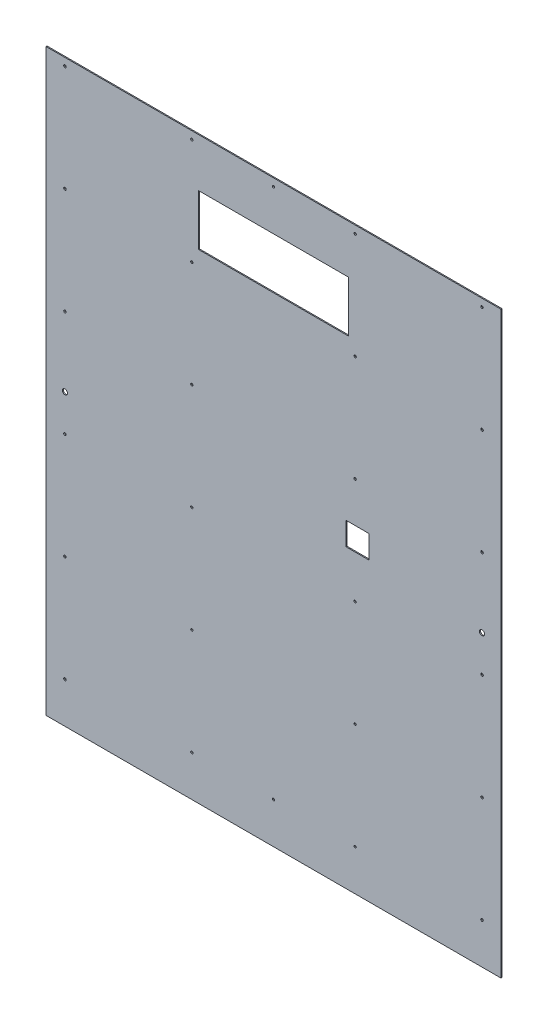
SolidWorks part; units mm, degrees
ref_plane "Спереди" through (0, 0, 0) normal (0, 0, 1) x (1, 0, 0)
ref_plane "Сверху" through (0, 0, 0) normal (0, 1, 0) x (1, 0, 0)
ref_plane "Справа" through (0, 0, 0) normal (1, 0, 0) x (0, 0, -1)
sketch "Эскиз1" plane through (0, 0, 0) normal (0, 0, 1) x (1, 0, 0)
  line L0 (445.5, 0) -> (445.5, 1135) construction
  line L1 (0, 0) -> (891, 0)
  line L2 (0, 0) -> (0, 1135)
  line L3 (0, 1135) -> (891, 1135)
  line L4 (891, 0) -> (891, 1135)
  line L6 (285.5, 0) -> (285.5, 1135) construction
  line L7 (285.5, 80) -> (605.5, 80) construction
  line L8 (605.5, 0) -> (605.5, 1135) construction
  line L9 (605.5, 80) -> (285.5, 288) construction
  line L10 (285.5, 288) -> (605.5, 288) construction
  line L11 (605.5, 288) -> (285.5, 496) construction
  line L12 (285.5, 496) -> (605.5, 496) construction
  line L13 (605.5, 496) -> (285.5, 704) construction
  line L14 (285.5, 704) -> (605.5, 704) construction
  line L15 (605.5, 704) -> (285.5, 912) construction
  line L16 (285.5, 912) -> (605.5, 912) construction
  line L17 (605.5, 912) -> (285.5, 1120) construction
  line L18 (285.5, 1120) -> (605.5, 1120) construction
  line L19 (270.3147, 65) -> (622.3147, 65) construction
  circle A0 centre (285.5, 912) radius 2.25
  circle A1 centre (285.5, 704) radius 2.25
  circle A2 centre (285.5, 496) radius 2.25
  circle A3 centre (285.5, 288) radius 2.25
  circle A4 centre (285.5, 80) radius 2.25
  circle A5 centre (445.5, 80) radius 2.25
  circle A6 centre (605.5, 80) radius 2.25
  circle A7 centre (605.5, 288) radius 2.25
  circle A8 centre (605.5, 496) radius 2.25
  circle A9 centre (605.5, 704) radius 2.25
  circle A10 centre (605.5, 912) radius 2.25
  circle A11 centre (605.5, 1120) radius 2.25
  circle A12 centre (445.5, 1120) radius 2.25
  circle A13 centre (285.5, 1120) radius 2.25
  dimension "D9" = 4.5
  dimension "D1" = 1135
  dimension "D2" = 891
  dimension "D3" = 160
  dimension "D4" = 160
  dimension "D5" = 15
  dimension "D6" = 15
  dimension "D7" = 208
  dimension "D8" = 208
base flange "Базовая кромка1" sketch "Эскиз1" thickness 2 reverse thickness direction no parameters "D1"=0.7366
sketch "Эскиз7" plane through (0, 0, -2) normal (0, 0, -1) x (-1, 0, 0)
  line L1 (-592.6742, 1040) -> (-298.3147, 1040)
  line L2 (-592.6742, 1040) -> (-592.6742, 940)
  line L3 (-592.6742, 940) -> (-298.3147, 940)
  line L4 (-298.3147, 1040) -> (-298.3147, 940)
extrude "Вырез-Вытянуть1" cut sketch "Эскиз7" against normal up to next normal cut yes
sketch "Эскиз8" plane through (0, 0, -2) normal (0, 0, -1) x (-1, 0, 0)
  circle A0 centre (-36.894, 567.5) radius 5
  circle A1 centre (-854.0149, 567.5) radius 5
extrude "Вырез-Вытянуть2" cut sketch "Эскиз8" against normal up to next normal cut yes
sketch "Эскиз9" plane through (0, 0, 0) normal (0, 0, 1) x (1, 0, 0)
  line L1 (587.3147, 625) -> (632.3147, 625)
  line L2 (587.3147, 625) -> (587.3147, 580)
  line L3 (587.3147, 580) -> (632.3147, 580)
  line L4 (632.3147, 625) -> (632.3147, 580)
  line L7 (622.3147, 590) -> (622.3147, 615) construction
  line L8 (622.3147, 615) -> (597.3147, 615) construction
  dimension "D1" = 45
  dimension "D2" = 45
  dimension "D3" = 10
  dimension "D4" = 10
extrude "Вырез-Вытянуть3" cut sketch "Эскиз9" against normal up to next normal cut yes
sketch "Эскиз10" plane through (0, 0, -2) normal (0, 0, -1) x (-1, 0, 0)
  circle A0 centre (-854.095, 1120) radius 2.5
  circle A1 centre (-854.095, 912) radius 2.5
  circle A2 centre (-854.095, 704) radius 2.5
  circle A3 centre (-854.095, 496) radius 2.5
  circle A4 centre (-854.095, 288) radius 2.5
  circle A5 centre (-854.095, 80) radius 2.5
  circle A6 centre (-36.894, 1120) radius 2.5
  circle A7 centre (-36.894, 912) radius 2.5
  circle A8 centre (-36.894, 704) radius 2.5
  circle A9 centre (-36.894, 496) radius 2.5
  circle A10 centre (-36.894, 288) radius 2.5
  circle A11 centre (-36.894, 80) radius 2.5
  dimension "D1" = 5
extrude "Вырез-Вытянуть4" cut sketch "Эскиз10" against normal up to next normal cut yes
sketch "Сгиб-Линии1" plane through (0, 0, 0) normal (0, 1, 0) x (1, 0, 0)
sketch "Граничная рамка1" plane through (0, 0, 0) normal (0, 1, 0) x (1, 0, 0)
sheet metal parameters "Листовой металл3" thickness 2 parameters "D1"=0.7366
flat pattern "Развертка3" [suppressed]
sketch "Сгиб-Линии2" plane through (0, 0, 0) normal (0, 1, 0) x (1, 0, 0)
sketch "Граничная рамка2" [suppressed] plane through (0, 0, 0) normal (0, 1, 0) x (1, 0, 0)
sheet metal parameters "Листовой металл4" thickness 2 parameters "D1"=0.7366
flat pattern "Развертка3"
sketch "Сгиб-Линии2" plane through (0, 0, 0) normal (0, 1, 0) x (1, 0, 0)
sketch "Граничная рамка2" [suppressed] plane through (0, 0, 0) normal (0, 1, 0) x (1, 0, 0)
sheet metal parameters "Листовой металл5" thickness 2 parameters "D1"=0.7366
flat pattern "Развертка3"
sketch "Сгиб-Линии2" plane through (0, 0, 0) normal (0, 1, 0) x (1, 0, 0)
sketch "Граничная рамка2" [suppressed] plane through (0, 0, 0) normal (0, 1, 0) x (1, 0, 0)
sheet metal parameters "Листовой металл6" thickness 2 parameters "D1"=0.7366
flat pattern "Развертка3"
sketch "Сгиб-Линии2" plane through (0, 0, 0) normal (0, 1, 0) x (1, 0, 0)
sketch "Граничная рамка2" [suppressed] plane through (0, 0, 0) normal (0, 1, 0) x (1, 0, 0)
sheet metal parameters "Листовой металл7" thickness 2 parameters "D1"=0.7366
flat pattern "Развертка3"
sketch "Сгиб-Линии2" plane through (0, 0, 0) normal (0, 1, 0) x (1, 0, 0)
sketch "Граничная рамка2" [suppressed] plane through (0, 0, 0) normal (0, 1, 0) x (1, 0, 0)
